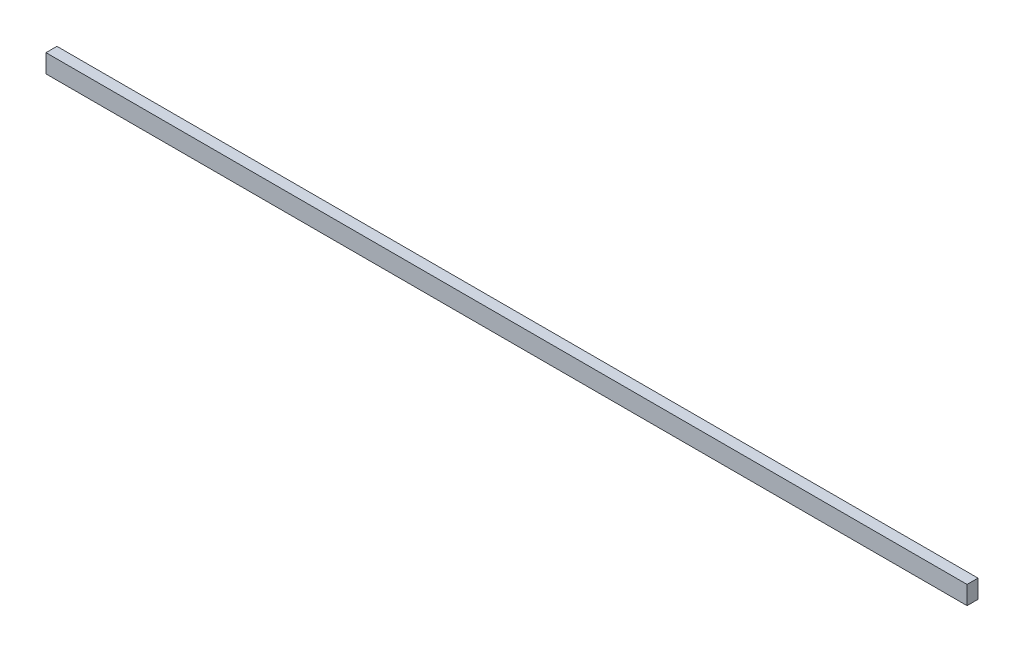
SolidWorks part; units mm, degrees
ref_plane "Plan de face" through (0, 0, 0) normal (0, 0, 1) x (1, 0, 0)
ref_plane "Plan de dessus" through (0, 0, 0) normal (0, 1, 0) x (1, 0, 0)
ref_plane "Plan de droite" through (0, 0, 0) normal (1, 0, 0) x (0, 0, -1)
sketch "Esquisse1" plane through (0, 0, 0) normal (0, 0, 1) x (1, 0, 0)
  line L1 (0, 0) -> (1850, 0)
  line L2 (0, 0) -> (0, 37)
  line L3 (0, 37) -> (1850, 37)
  line L4 (1850, 0) -> (1850, 37)
  dimension "D1" = 37
  dimension "D2" = 1850
extrude "Boss.-Extru.1" add sketch "Esquisse1" along normal blind 22
